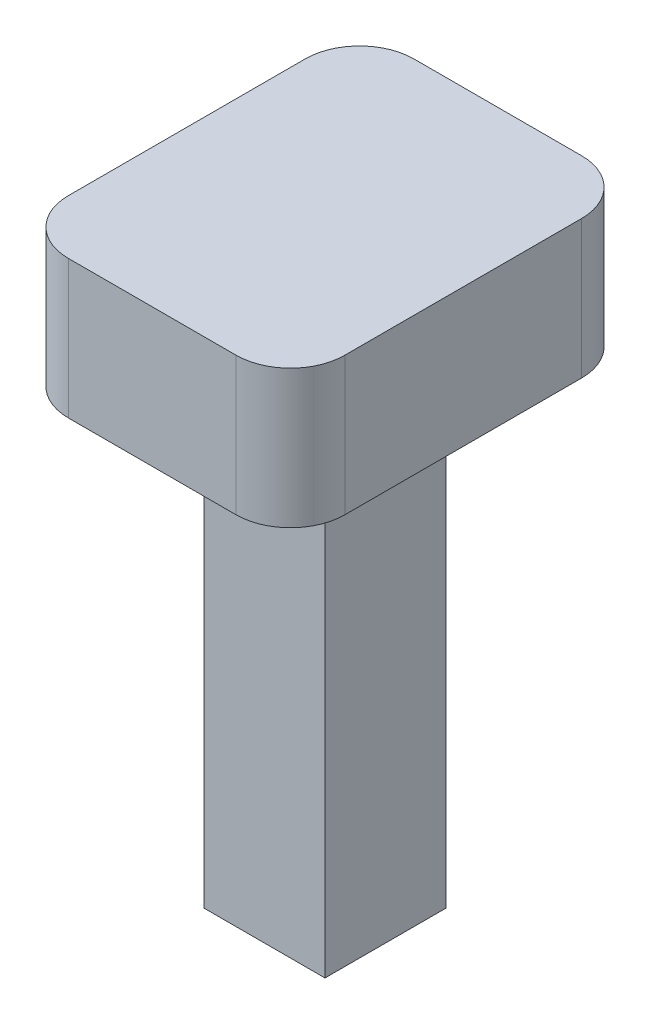
SolidWorks part; units mm, degrees
ref_plane "Front Plane" through (0, 0, 0) normal (0, 0, 1) x (1, 0, 0)
ref_plane "Top Plane" through (0, 0, 0) normal (0, 1, 0) x (1, 0, 0)
ref_plane "Right Plane" through (0, 0, 0) normal (1, 0, 0) x (0, 0, -1)
sketch "Sketch1" plane through (0, 0, 0) normal (0, 1, 0) x (1, 0, 0)
  line L1 (-1.3875, 1.3875) -> (1.3875, 1.3875)
  line L2 (-1.3875, 1.3875) -> (-1.3875, -1.3875)
  line L3 (-1.3875, -1.3875) -> (1.3875, -1.3875)
  line L4 (1.3875, 1.3875) -> (1.3875, -1.3875)
  line L5 (0, -1.3875) -> (0, 1.3875) construction
  line L6 (-1.3875, 0) -> (1.3875, 0) construction
  point P0 (0, 0)
  dimension "D1" = 2.775
  dimension "D2" = 2.775
extrude "Boss-Extrude1" add sketch "Sketch1" along normal blind 10.775
sketch "Sketch2" plane through (0, 10.775, 0) normal (0, 1, 0) x (1, 0, 0)
  line L1 (-3.175, 3.9688) -> (3.175, 3.9688)
  line L2 (-3.175, 3.9688) -> (-3.175, -3.9688)
  line L3 (-3.175, -3.9688) -> (3.175, -3.9688)
  line L4 (3.175, 3.9688) -> (3.175, -3.9688)
  line L5 (0, -3.9688) -> (0, 3.9688) construction
  line L6 (-3.175, 0) -> (3.175, 0) construction
  point P0 (0, 0)
  dimension "D1" = 7.9375
  dimension "D2" = 6.35
extrude "Boss-Extrude2" add sketch "Sketch2" along normal blind 3.175
fillet "Fillet1" radius 1.25 8 edges at (0, 10.775, -1.3875) (1.3875, 10.775, 0) (0, 10.775, 1.3875) (-1.3875, 10.775, 0) (-3.175, 12.3625, -3.9688) (3.175, 12.3625, -3.9688) (-3.175, 12.3625, 3.9688) (3.175, 12.3625, 3.9688)
equation "\"2.875inmm\"=2.875"
